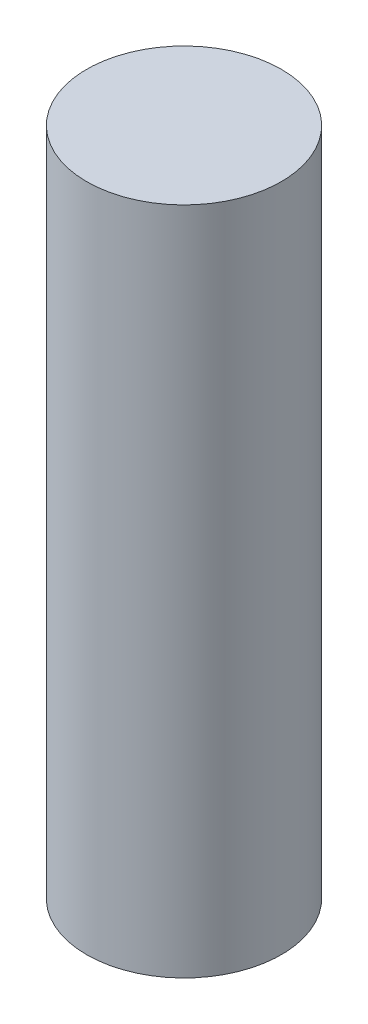
SolidWorks part; units mm, degrees
ref_plane "Front Plane" through (0, 0, 0) normal (0, 0, 1) x (1, 0, 0)
ref_plane "Top Plane" through (0, 0, 0) normal (0, 1, 0) x (1, 0, 0)
ref_plane "Right Plane" through (0, 0, 0) normal (1, 0, 0) x (0, 0, -1)
sketch "Sketch1" plane through (0, 0, 0) normal (0, 1, 0) x (1, 0, 0)
  circle A0 centre (0, 0) radius 6.0198
  dimension "D1" = 12.0396
extrude "Boss-Extrude1" add sketch "Sketch1" along normal mid plane 41.402
ref_axis "Axis1" through (0, 22.7711, 0) along (0, -1, 0)
